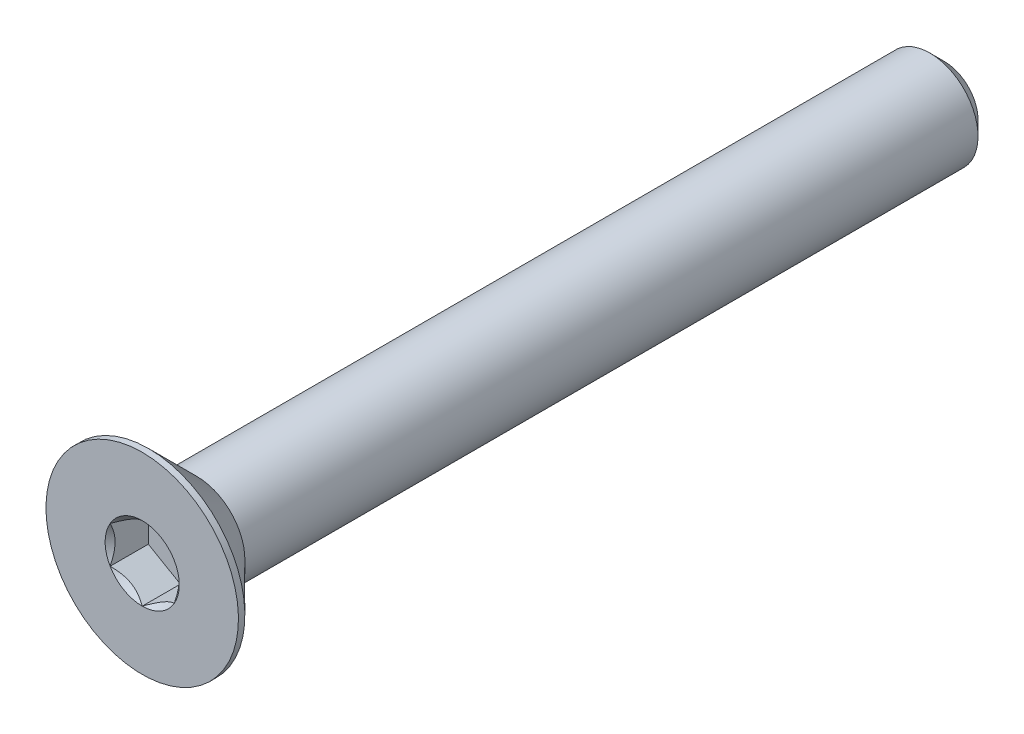
SolidWorks part; units mm, degrees
material "Alloy Steel"
ref_plane "Front" through (0, 0, 0) normal (0, 0, 1) x (1, 0, 0)
ref_plane "Top" through (0, 0, 0) normal (0, 1, 0) x (1, 0, 0)
ref_plane "Right" through (0, 0, 0) normal (1, 0, 0) x (0, 0, -1)
sketch "Sketch1" plane through (0, 0, 0) normal (1, 0, 0) x (0, 0, -1)
  line L0 (-12.5, 3) -> (-12.3, 3) construction
  line L1 (-12.3, 3) -> (-10.8, 1.5) construction
  line L2 (-12.5, 1.5) -> (12.5, 1.5) construction
  line L3 (12.5, 1.5) -> (12.5, 0) construction
  line L4 (12.5, 0) -> (-12.5, 0) construction
  line L5 (-12.5, 0) -> (-12.5, 3) construction
  line L6 (-12.5, 3) -> (-12.5, -3) construction
  line L7 (12.5, 1.5) -> (12.5, -1.5) construction
  line L8 (-12.5, -3) -> (-12.3, -3) construction
  line L9 (-12.3, -3) -> (-10.8, -1.5) construction
  line L11 (-12.5, 1.5) -> (-12.5, 0) construction
  line L12 (-10.8, 1.5) -> (-10.8, 0) construction
  line L13 (12.4688, 1.5541) -> (12.7188, 1.1211) construction
  line L14 (12.7188, 1.1211) -> (12.9688, 1.5541) construction
  line L15 (12.9688, 1.5541) -> (12.4688, 1.5541) construction
  line L16 (12.7188, 1.5541) -> (12.7188, 1.5) construction
  line L17 (12.7188, 1.5) -> (12.7188, 1.1752) construction
  line L18 (12.7188, 1.1752) -> (12.7188, 1.1211) construction
  line L19 (12.7188, 1.5271) -> (12.9531, 1.5271) construction
  line L20 (12.7188, 1.5271) -> (12.4844, 1.5271) construction
  line L21 (12.5, 1.5) -> (12.9375, 1.5) construction
  line L22 (12.6875, 1.1752) -> (12.75, 1.1752) construction
  line L23 (12.5, -1.5) -> (-10.8, -1.5) construction
  point P10 (11.25, -1.5)
  point P24 (-10.8, 1.5)
  point P30 (0, 0)
  dimension "Head Diameter" = 6
  dimension "Head Height" = 1.7
  dimension "Length" = 25
  dimension "Countersink Angle" = 90
  dimension "Thread Pitch" = 0.5
  dimension "D2" = 0.0625
  dimension "Minimum Thread Length" = 23.3
  dimension "Thread Size" = 3
  dimension "D1" = 1.25
sketch "Sketch2" plane through (0, 0, 0) normal (0, 0, 1) x (1, 0, 0)
  line L1 (0, 1.1547) -> (-1, 0.5774) construction
  line L2 (-1, 0.5774) -> (-1, -0.5774) construction
  line L3 (-1, -0.5774) -> (0, -1.1547) construction
  line L4 (0, -1.1547) -> (1, -0.5774) construction
  line L5 (1, -0.5774) -> (1, 0.5774) construction
  line L6 (1, 0.5774) -> (0, 1.1547) construction
  circle A0 centre (0, 0) radius 1 construction
  dimension "Drive Size" = 2
sketch "Sketch3" plane through (0, 0, 0) normal (1, 0, 0) x (0, 0, -1)
  line L0 (-12.5, 1.5) -> (12.5, 1.5)
  line L1 (12.5, 1.5) -> (12.5, 0)
  line L2 (12.5, 0) -> (-12.5, 0)
  line L3 (-12.5, 0) -> (-12.5, 1.5)
revolve "Revolve1" add sketch "Sketch3" angle 360 about L4
chamfer "Chamfer1" distance 0.45 angle 45 1 edges at (0, 1.5, -12.5)
sketch "Sketch6" plane through (0, 0, 0) normal (1, 0, 0) x (0, 0, -1)
  line L0 (-12.5, 3) -> (-12.3, 3)
  line L1 (-12.3, 3) -> (-10.8, 1.5)
  line L2 (-10.8, 1.5) -> (-10.8, 0)
  line L3 (-10.8, 0) -> (-12.5, 0)
  line L4 (-12.5, 0) -> (-12.5, 3)
revolve "Revolve2" add sketch "Sketch6" angle 360 about L4
sketch "Sketch8" plane through (0, 0, 12.5) normal (0, 0, 1) x (1, 0, 0)
  line L0 (0, 1.1547) -> (-1, 0.5774) construction
  line L1 (1, 0.5774) -> (0, 1.1547) construction
  line L2 (1, -0.5774) -> (1, 0.5774) construction
  line L3 (0, -1.1547) -> (1, -0.5774) construction
  line L4 (-1, 0.5774) -> (-1, -0.5774) construction
  line L5 (-1, -0.5774) -> (0, -1.1547) construction
  line L6 (0, 1.1547) -> (-1, 0.5774)
  line L7 (1, 0.5774) -> (0, 1.1547)
  line L8 (1, -0.5774) -> (1, 0.5774)
  line L9 (0, -1.1547) -> (1, -0.5774)
  line L10 (-1, 0.5774) -> (-1, -0.5774)
  line L11 (-1, -0.5774) -> (0, -1.1547)
extrude "Cut-Extrude1" cut sketch "Sketch8" against normal blind 1.19
sketch "Sketch9" plane through (0, 0, 12.5) normal (0, 0, 1) x (1, 0, 0)
  circle A0 centre (0, 0) radius 1.1547
extrude "Cut-Extrude2" cut sketch "Sketch9" against normal up to next (1.19 mm away) draft 45
ref_plane "Plane1" [suppressed] through (0, 0, 10.8) normal (0, 0, 1) x (1, 0, 0)
split "Split1" [suppressed] bodies to split 124
sketch "Sketch4" [suppressed] plane through (0, 0, -12.5) normal (0, 0, -1) x (-1, 0, 0)
  circle A0 centre (0, 0) radius 1.5 construction
  circle A1 centre (0, 0) radius 1.5
curve "Helix/Spiral1" [suppressed] pitch 0.5 height 23.8 turns 47.6
sketch "Sketch10" [suppressed] plane through (0, 0, 0) normal (1, 0, 0) x (0, 0, -1)
  line L0 (12.4844, 1.5271) -> (12.9531, 1.5271)
  line L1 (12.9531, 1.5271) -> (12.75, 1.1752)
  line L2 (12.75, 1.1752) -> (12.6875, 1.1752)
  line L3 (12.6875, 1.1752) -> (12.4844, 1.5271)
sweep "Cut-Sweep1" [suppressed] cut profiles "Sketch10" path "Helix/Spiral1"
equation "\"D2@Sketch1\" = \"Thread Pitch@Sketch1\" / 8"
equation "\"D4@Helix/Spiral1\"=\"Thread Pitch@Sketch1\""
equation "\"D3@Helix/Spiral1\"=\"Minimum Thread Length@Sketch1\"+\"Thread Pitch@Sketch1\""
equation "\"D1@Chamfer1\"=\"Thread Size@Sketch1\"*.15"
equation "\"D1@Cut-Extrude1\"=\"Head Height@Sketch1\"*.7"
equation "\"D1@Sketch1\"=\"Thread Pitch@Sketch1\"*2.5"
